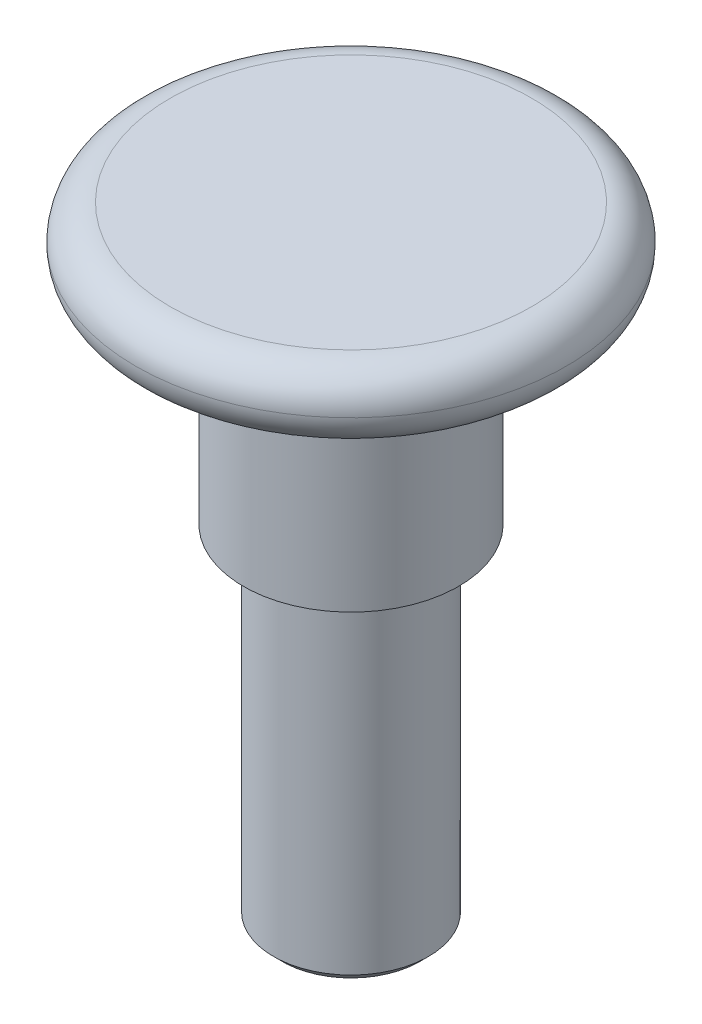
SolidWorks part; units mm, degrees
ref_plane "Plano frontal" through (0, 0, 0) normal (0, 0, 1) x (1, 0, 0)
ref_plane "Plano superior" through (0, 0, 0) normal (0, 1, 0) x (1, 0, 0)
ref_plane "Plano direito" through (0, 0, 0) normal (1, 0, 0) x (0, 0, -1)
sketch "Esboço1" plane through (0, 0, 0) normal (0, 0, 1) x (1, 0, 0)
  line L0 (0, -74.7162) -> (0, 63.9571) construction
  line L1 (0, 63.9571) -> (12.5, 63.9571)
  line L2 (12.5, 63.9571) -> (12.5, 59.9571)
  line L3 (12.5, 59.9571) -> (6.25, 59.9571)
  line L4 (6.25, 59.9571) -> (6.25, 47.7571)
  line L5 (6.25, 47.7571) -> (4.5, 47.7571)
  line L6 (4.5, 47.7571) -> (4.5, 27.7571)
  line L7 (4.5, 27.7571) -> (0, 27.7571)
  line L8 (0, 63.9571) -> (0, 27.7571)
  dimension "D1" = 4.5
  dimension "D2" = 6.25
  dimension "D3" = 12.5
  dimension "D4" = 4
  dimension "D5" = 12.2
  dimension "D6" = 20
revolve "Revolução1" add sketch "Esboço1" angle 360 about L0
fillet "Filete1" radius 2 2 edges at (0, 59.9571, -12.5) (0, 63.9571, -12.5)
chamfer "Chanfro1" distance 0.5 angle 45 1 edges at (0, 27.7571, -4.5)
